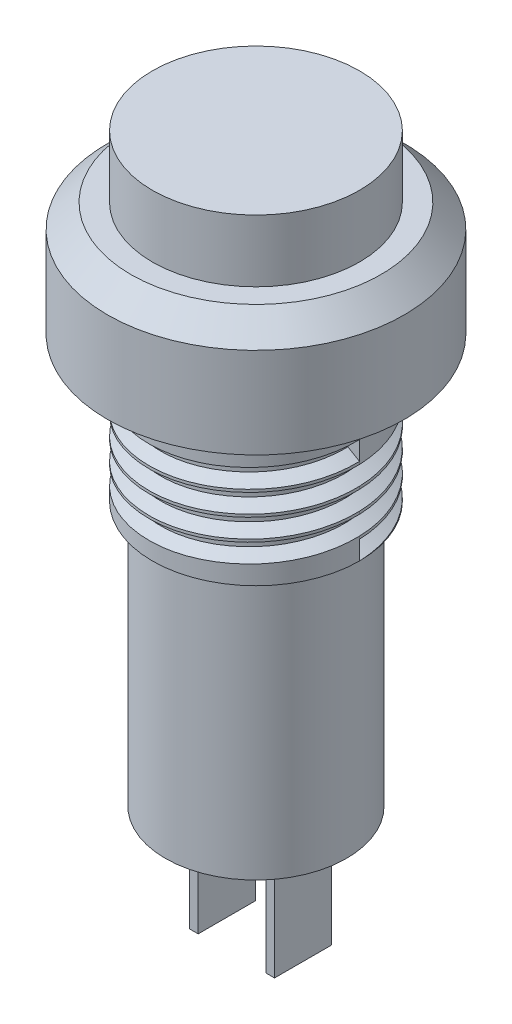
SolidWorks part; units mm, degrees
ref_plane "Płaszczyzna przednia" through (0, 0, 0) normal (0, 0, 1) x (1, 0, 0)
ref_plane "Płaszczyzna górna" through (0, 0, 0) normal (0, 1, 0) x (1, 0, 0)
ref_plane "Płaszczyzna prawa" through (0, 0, 0) normal (1, 0, 0) x (0, 0, -1)
sketch "Szkic1" plane through (0, 0, 0) normal (0, 1, 0) x (1, 0, 0)
  circle A0 centre (0, 0) radius 5.25
extrude "Dodanie-wyciągnięcie1" add sketch "Szkic1" along normal blind 15.3
sketch "Szkic2" plane through (0, 15.3, 0) normal (0, 1, 0) x (1, 0, 0)
  circle A0 centre (0, 0) radius 6
extrude "Dodanie-wyciągnięcie2" add sketch "Szkic2" along normal blind 8.4
sketch "Szkic3" plane through (0, 23.7, 0) normal (0, 1, 0) x (1, 0, 0)
  circle A0 centre (0, 0) radius 8.6
extrude "Dodanie-wyciągnięcie3" add sketch "Szkic3" along normal blind 6.6
chamfer "Sfazowanie1" distance 1.35 angle 45 1 edges at (0, 30.3, 8.6)
sketch "Szkic4" plane through (0, 30.3, 0) normal (0, 1, 0) x (1, 0, 0)
  circle A0 centre (0, 0) radius 6
extrude "Dodanie-wyciągnięcie4" add sketch "Szkic4" along normal blind 3.6
thread "Gwint1" pitch 1.25 method cut profile "Profil gwintu2" start angle 0, offset 0, length 5, pitch 1.25, diameter 12
ref_plane "Płaszczyzna2" through (6, 15.3, 0) normal (0, 0, 1) x (1, 0, 0)
sketch "Profil gwintu2" plane through (6, 15.3, 0) normal (0, 0, 1) x (1, 0, 0)
  line L0 (0, 0) -> (0, 1.25) construction
  line L11 (0, 0) -> (0, 1.0937)
  line L12 (0, 1.0937) -> (-0.6766, 0.7031)
  line L13 (-0.6766, 0.7031) -> (-0.6766, 0.3906)
  line L15 (-0.6766, 0.3906) -> (0, 0)
  line L17 (-0.6766, 0.5469) -> (0, 0.5469) construction
  point P2 (0, 0)
  dimension "Pitch" = 1.25
  dimension "Profile_Angle" = 60
  dimension "Profile_Land" = 0.3125
  dimension "Profile_Height" = 0.6766
sketch "Szkic15" plane through (0, 0, 0) normal (0, -1, 0) x (1, 0, 0)
  line L0 (0, 0) -> (0, 9.7349) construction
  line L1 (-2.4625, 1.3862) -> (-1.9625, 1.3862)
  line L2 (-2.4625, 1.3862) -> (-2.4625, -1.9259)
  line L3 (-2.4625, -1.9259) -> (-1.9625, -1.9259)
  line L4 (-1.9625, 1.3862) -> (-1.9625, -1.9259)
  line L5 (1.9625, 1.3862) -> (1.9625, -1.9259)
  line L6 (2.4625, -1.9259) -> (1.9625, -1.9259)
  line L7 (2.4625, 1.3862) -> (2.4625, -1.9259)
  line L8 (2.4625, 1.3862) -> (1.9625, 1.3862)
  dimension "D1" = 0.5
extrude "Dodanie-wyciągnięcie5" add sketch "Szkic15" along normal blind 6.7
ref_plane "Płaszczyzna3" through (0, 0, -0.2698) normal (0, 0, -1) x (-1, 0, 0)
